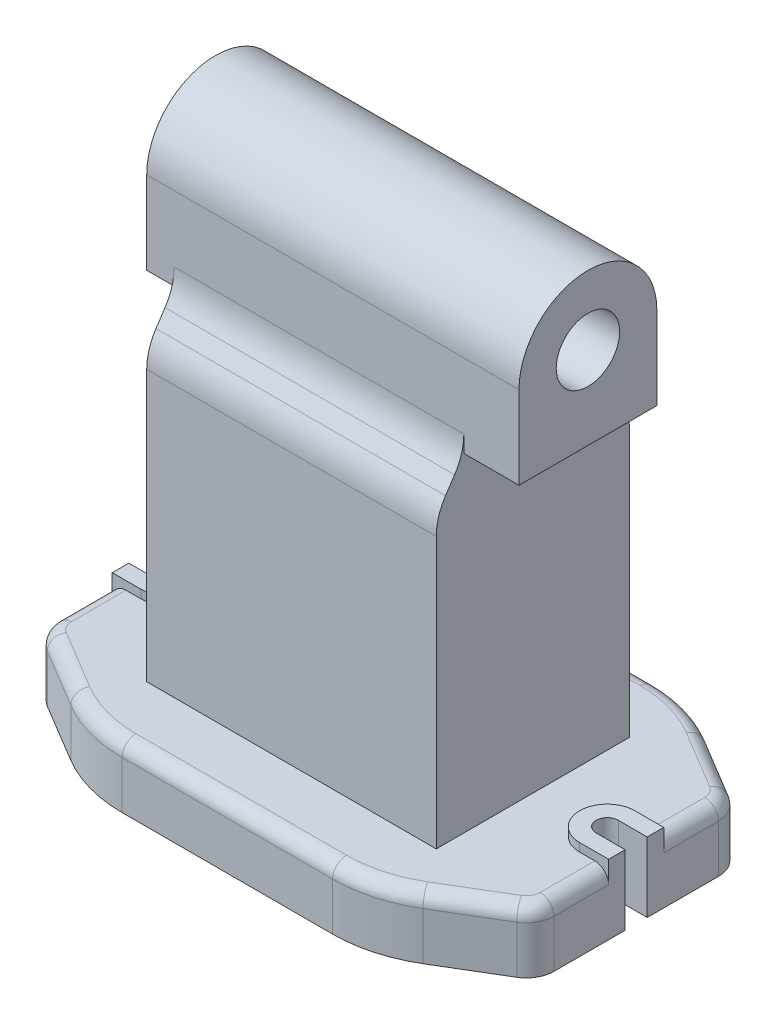
SolidWorks part; units mm, degrees
ref_plane "Front Plane" through (0, 0, 0) normal (0, 0, 1) x (1, 0, 0)
ref_plane "Top Plane" through (0, 0, 0) normal (0, 1, 0) x (1, 0, 0)
ref_plane "Right Plane" through (0, 0, 0) normal (1, 0, 0) x (0, 0, -1)
sketch "Sketch1" plane through (0, 0, 0) normal (0, 1, 0) x (1, 0, 0)
  line L0 (-27.5, 54.25) -> (-38, 54.25)
  line L1 (0, 0) -> (104, 0)
  line L3 (0, 116.5) -> (104, 116.5)
  line L5 (-38, 22.75) -> (0, 0)
  line L6 (-38, 54.25) -> (-38, 22.75)
  line L7 (-27.5, 62.25) -> (-38, 62.25)
  line L8 (-38, 62.25) -> (-38, 93.75)
  line L9 (-38, 93.75) -> (0, 116.5)
  line L10 (-38, 54.25) -> (-38, 62.25) construction
  line L11 (-38, 58.25) -> (142, 58.25) construction
  line L12 (52, 116.5) -> (52, 0) construction
  line L13 (142, 54.25) -> (142, 22.75)
  line L14 (142, 22.75) -> (104, 0)
  line L15 (131.5, 54.25) -> (142, 54.25)
  line L16 (131.5, 62.25) -> (142, 62.25)
  line L17 (142, 62.25) -> (142, 93.75)
  line L18 (142, 93.75) -> (104, 116.5)
  line L19 (142, 54.25) -> (142, 62.25) construction
  arc A0 (-27.5, 54.25) -> (-27.5, 62.25) centre (-27.5, 58.25) ccw
  arc A1 (131.5, 54.25) -> (131.5, 62.25) centre (131.5, 58.25) cw
  dimension "D3" = 4
  dimension "D1" = 71
  dimension "D2" = 116.5
  dimension "D4" = 180
  dimension "D5" = 104
  dimension "D6" = 10.5
extrude "Base" add sketch "Sketch1" along normal blind 22.3
sketch "Sketch3" plane through (0, 22.3, 0) normal (0, 1, 0) x (1, 0, 0)
  line L0 (-27.5, 54.25) -> (-38, 54.25) construction
  line L1 (-38, 62.25) -> (-27.5, 62.25) construction
  line L2 (-27.5, 54.25) -> (-38, 54.25)
  line L3 (-38, 62.25) -> (-27.5, 62.25)
  line L8 (52, 0) -> (52, 116.5) construction
  line L9 (0, 0) -> (104, 0) construction
  line L10 (104, 116.5) -> (0, 116.5) construction
  line L11 (-38, 68.25) -> (-27.5, 68.25)
  line L12 (-27.5, 48.25) -> (-38, 48.25)
  line L13 (-38, 68.25) -> (-38, 62.25)
  line L14 (-38, 54.25) -> (-38, 48.25)
  line L15 (142, 54.25) -> (142, 48.25)
  line L16 (142, 68.25) -> (142, 62.25)
  line L17 (131.5, 48.25) -> (142, 48.25)
  line L18 (142, 68.25) -> (131.5, 68.25)
  line L19 (142, 62.25) -> (131.5, 62.25)
  line L20 (131.5, 54.25) -> (142, 54.25)
  arc A0 (-27.5, 54.25) -> (-27.5, 62.25) centre (-27.5, 58.25) ccw construction
  arc A1 (-27.5, 54.25) -> (-27.5, 62.25) centre (-27.5, 58.25) ccw
  arc A3 (-27.5, 48.25) -> (-27.5, 68.25) centre (-27.5, 58.25) ccw
  arc A4 (131.5, 48.25) -> (131.5, 68.25) centre (131.5, 58.25) cw
  arc A5 (131.5, 54.25) -> (131.5, 62.25) centre (131.5, 58.25) cw
  dimension "D1" = 6
extrude "Resalto - Furos de Fixação" add sketch "Sketch3" along normal blind 3
sketch "Sketch4" plane through (0, 22.3, 0) normal (0, 1, 0) x (1, 0, 0)
  line L0 (52, 116.5) -> (52, 0) construction
  line L1 (104, 116.5) -> (0, 116.5) construction
  line L2 (0, 0) -> (104, 0) construction
  line L4 (-0.5, 23.25) -> (104.5, 23.25)
  line L5 (-0.5, 23.25) -> (-0.5, 93.25)
  line L6 (-0.5, 93.25) -> (104.5, 93.25)
  line L7 (104.5, 23.25) -> (104.5, 93.25)
  line L8 (-0.5, 23.25) -> (104.5, 93.25) construction
  line L9 (-0.5, 93.25) -> (104.5, 23.25) construction
  point P6 (52, 58.25)
  dimension "105" = 105
  dimension "D2" = 70
extrude "Corpo Retangular" add sketch "Sketch4" along normal blind 104.2
sketch "Sketch5" plane through (-0.5, 0, 0) normal (-1, 0, 0) x (0, 0, 1)
  line L0 (-58.25, 171.5) -> (-58.25, 25.3) construction
  line L1 (-33.25, 171.5) -> (-33.25, 141.5)
  line L2 (-54.25, 25.3) -> (-62.25, 25.3) construction
  line L3 (-93.25, 22.3) -> (-23.25, 22.3) construction
  line L4 (-83.25, 171.5) -> (-83.25, 141.5)
  line L5 (-83.25, 141.5) -> (-93.25, 126.5)
  line L6 (-33.25, 141.5) -> (-23.25, 126.5)
  line L7 (-93.25, 126.5) -> (-23.25, 126.5)
  line L8 (-83.25, 141.5) -> (-33.25, 141.5)
  circle A0 centre (-58.25, 171.5) radius 11.5
  arc A1 (-33.25, 171.5) -> (-83.25, 171.5) centre (-58.25, 171.5) ccw
  line M11 (-23.25, 126.5) -> (-93.25, 126.5)
  dimension "D2" = 50
  dimension "D3" = 23
  dimension "D1" = 149.2
  dimension "D4" = 30
extrude "Corpo Inclinado" add sketch "Sketch5" against normal blind 105 contours L0 L8 L5 L7 | L8 L0 L6 M11 region at (-0.5, 133.5833, -43.1111) region at (-0.5, 133.5833, -73.3889)
extrude "Corpo Arredondado - Back" add sketch "Sketch5<4>" along normal blind 10 separate body contours A0 L8 L1 A1 L4 region at (-0.5, 156.5, -33.9933)
sketch "Sketch5<4>" plane through (-0.5, 0, 0) normal (-1, 0, 0) x (0, 0, 1) same geometry as "Sketch5"
extrude "Corpo Arredondado - Front" add sketch "Sketch5<5>" against normal blind 125 contours A0 L8 L1 A1 L4 region at (-0.5, 156.5, -33.9933)
sketch "Sketch5<5>" plane through (-0.5, 0, 0) normal (-1, 0, 0) x (0, 0, 1) same geometry as "Sketch5"
sketch "Sketch9" plane through (0, 0, 0) normal (0, -1, 0) x (1, 0, 0)
  line L0 (127.5, -58.25) -> (-23.5, -58.25) construction
  line L1 (52, 0) -> (52, -116.5) construction
  line L2 (0, 0) -> (104, 0) construction
  line L3 (104, -116.5) -> (0, -116.5) construction
  arc A0 (131.5, -54.25) -> (131.5, -62.25) centre (131.5, -58.25) ccw construction
  arc A1 (-27.5, -62.25) -> (-27.5, -54.25) centre (-27.5, -58.25) ccw construction
  circle A2 centre (2.5, -58.25) radius 4
  circle A3 centre (101.5, -58.25) radius 4
  dimension "D1" = 8
  dimension "D2" = 99
  dimension "D3" = 49.5
extrude "Pinos Guia" add sketch "Sketch9" along normal blind 20
fillet "Raios 50mm" radius 50 4 edges at (0, 11.15, -116.5) (104, 11.15, -116.5) (0, 11.15, 0) (104, 11.15, 0)
fillet "Raios 20mm" radius 20 4 edges at (52, 126.5, -93.25) (52, 141.5, -83.25) (52, 141.5, -33.25) (52, 126.5, -23.25)
fillet "Raios 10mm" radius 10 4 edges at (-38, 11.15, -93.75) (-38, 11.15, -22.75) (142, 11.15, -93.75) (142, 11.15, -22.75)
fillet "Raios 5mm" radius 5 18 edges at (142, 22.3, -78.1659) (140.6996, 22.3, -93.0129) (126.4984, 22.3, -103.0306) (103.5002, 22.3, -114.6922) (-38, 22.3, -78.1659) (-36.6996, 22.3, -93.0129) (-22.4984, 22.3, -103.0306) (0.4998, 22.3, -114.6922) (-38, 22.3, -38.3341) (-36.6996, 22.3, -23.4871) (-22.4984, 22.3, -13.4694) (0.4998, 22.3, -1.8078) (142, 22.3, -38.3341) (140.6996, 22.3, -23.4871) (126.4984, 22.3, -13.4694) (103.5002, 22.3, -1.8078) (52, 22.3, -116.5) (52, 22.3, 0)
sketch "Posição do Furo M10" plane through (-0.5, 0, 0) normal (-1, 0, 0) x (0, 0, 1)
  line L0 (-58.25, 183) -> (-58.25, 25.3) construction
  line L1 (-54.25, 25.3) -> (-62.25, 25.3) construction
  circle A0 centre (-58.25, 171.5) radius 11.5 construction
  circle A1 centre (-58.25, 121.5) radius 5
  dimension "D1" = 50
  dimension "D2" = 10
hole_wizard "Furo M10x50" positions "Sketch7" profile "Sketch8" tap size "M10x1.0" standard "ANSI Metric"
sketch "Sketch7" plane through (-0.5, 0, 0) normal (-1, 0, 0) x (0, 0, 1)
  point P0 (-58.25, 121.5)
sketch "Sketch8" plane through (-0.5, 121.5, -58.25) normal (0, 1, 0) x (0, 0, 1)
  line L0 (0, 0) -> (0, 50)
  line L1 (0, 50) -> (4.5, 47.2961)
  line L2 (4.5, 47.2961) -> (4.5, 0)
  line L5 (4.5, 0) -> (0, 0)
  line L10 (0, 50) -> (-4.5, 47.2961) construction
  line L11 (0, -6.35) -> (0, 107.95) construction
  dimension "Tap Drill Dia." = 9
  dimension "Tap Drill Depth" = 50
  dimension "Drill Angle" = 118
cosmetic thread "Hole Thread1" parameters "D1"=20, "D2"=10
